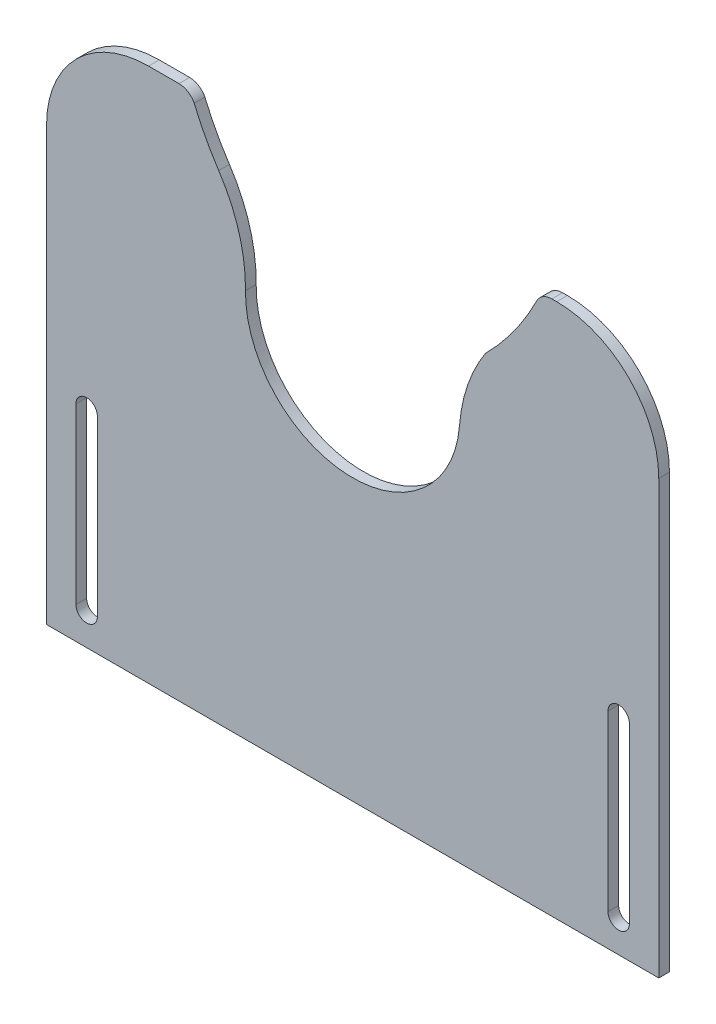
SolidWorks part; units mm, degrees
ref_plane "Front Plane" through (0, 0, 0) normal (0, 0, 1) x (1, 0, 0)
ref_plane "Top Plane" through (0, 0, 0) normal (0, 1, 0) x (1, 0, 0)
ref_plane "Right Plane" through (0, 0, 0) normal (1, 0, 0) x (0, 0, -1)
sketch "Sketch1" plane through (0, 0, 0) normal (0, 0, 1) x (1, 0, 0)
  line L0 (76.3333, 66.2897) -> (74.5053, 66.2897)
  line L1 (-64.9636, 66.2897) -> (-76.3333, 66.2897)
  line L2 (-114.5, 28.1231) -> (-114.5, -133.7103)
  line L3 (-114.5, -133.7103) -> (114.5, -133.7103)
  line L4 (114.5, -133.7103) -> (114.5, 28.1231)
  line L5 (0, -133.7103) -> (0, 66.2897) construction
  arc A0 (114.5, 28.1231) -> (76.3333, 66.2897) centre (76.3333, 28.1231) ccw
  arc A1 (74.5053, 66.2897) -> (68.8157, 62.7734) centre (74.5053, 59.9286) ccw
  arc A2 (49.7507, 36.3221) -> (68.8157, 62.7734) centre (-22.2171, 108.2899) ccw
  arc A3 (49.7507, 36.3221) -> (23.9676, 4.0557) centre (94.2687, -25.6853) ccw
  arc A4 (-1.3567, -13.7973) -> (23.9676, 4.0557) centre (0, 11.1658) ccw
  arc A5 (-23.9676, 4.0557) -> (-1.3567, -13.7973) centre (0, 11.1658) ccw
  arc A6 (-23.9676, 4.0557) -> (-43.1729, 36.3221) centre (-97.1487, -17.6537) ccw
  arc A7 (-59.274, 62.7734) -> (-43.1729, 36.3221) centre (34.7026, 101.8516) ccw
  arc A8 (-59.274, 62.7734) -> (-64.9636, 66.2897) centre (-64.9636, 59.9286) ccw
  arc A9 (-76.3333, 66.2897) -> (-114.5, 28.1231) centre (-76.3333, 28.1231) ccw
  dimension "D3" = 25
  dimension "D1" = 229
  dimension "D2" = 200
extrude "Boss-Extrude1" add sketch "Sketch1" along normal blind 4
sketch "Sketch2" plane through (0, 0, 4) normal (0, 0, 1) x (1, 0, 0)
  line L0 (-99.5, -56.7103) -> (-99.5, -121.7103) construction
  line L1 (-95.5, -56.7103) -> (-95.5, -121.7103)
  line L2 (-103.5, -56.7103) -> (-103.5, -121.7103)
  line L5 (-114.5, 28.1231) -> (-114.5, -133.7103) construction
  line L7 (-114.5, -133.7103) -> (114.5, -133.7103) construction
  line L8 (0, -133.7103) -> (0, 66.461) construction
  line L9 (99.5, -56.7103) -> (99.5, -121.7103) construction
  line L10 (95.5, -56.7103) -> (95.5, -121.7103)
  line L11 (103.5, -56.7103) -> (103.5, -121.7103)
  arc A0 (-95.5, -56.7103) -> (-103.5, -56.7103) centre (-99.5, -56.7103) ccw
  arc A1 (-103.5, -121.7103) -> (-95.5, -121.7103) centre (-99.5, -121.7103) ccw
  arc A2 (95.5, -56.7103) -> (103.5, -56.7103) centre (99.5, -56.7103) cw
  arc A3 (103.5, -121.7103) -> (95.5, -121.7103) centre (99.5, -121.7103) cw
  point P2 (-99.5, -89.2103)
  point P17 (99.5, -89.2103)
  dimension "D3" = 12
  dimension "D1" = 8
  dimension "D2" = 11
  dimension "D4" = 65
extrude "Cut-Extrude1" cut sketch "Sketch2" against normal blind 10
sketch "Sketch5" plane through (0, 0, 4) normal (0, 0, 1) x (1, 0, 0)
  circle A0 centre (0, 11.1658) radius 38.0915
  circle A1 centre (0, 11.1658) radius 38.0915
sketch "Sketch6" plane through (0, 0, 4) normal (0, 0, 1) x (1, 0, 0)
  circle A2 centre (0, 11.1658) radius 40.0915
  circle A3 centre (0, 11.1658) radius 40.0915
  dimension "D1" = 2
extrude "Cut-Extrude2" cut sketch "Sketch6" against normal blind 4
fillet "Fillet1" radius 60 2 edges at (-36.2272, 28.3391, 2) (37.5003, 25.3453, 2)
